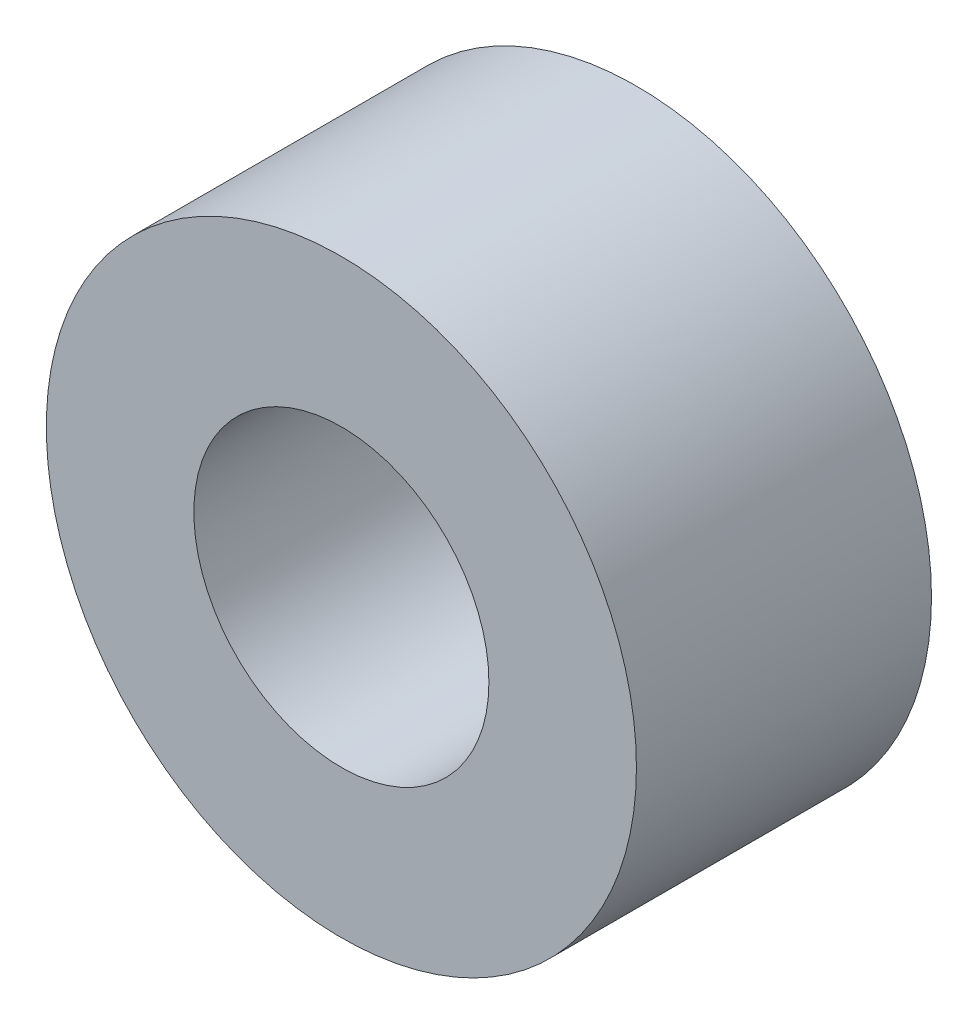
SolidWorks part; units mm, degrees
ref_plane "Alzado" through (0, 0, 0) normal (0, 0, 1) x (1, 0, 0)
ref_plane "Planta" through (0, 0, 0) normal (0, 1, 0) x (1, 0, 0)
ref_plane "Vista lateral" through (0, 0, 0) normal (1, 0, 0) x (0, 0, -1)
sketch "Croquis1" plane through (0, 0, 0) normal (0, 0, 1) x (1, 0, 0)
  circle A2 centre (54.9, 15.2) radius 2.5
  circle A3 centre (54.9, 15.2) radius 5
  dimension "D1" = 10
  dimension "D2" = 5
extrude "Saliente-Extruir1" add sketch "Croquis1" along normal blind 5
